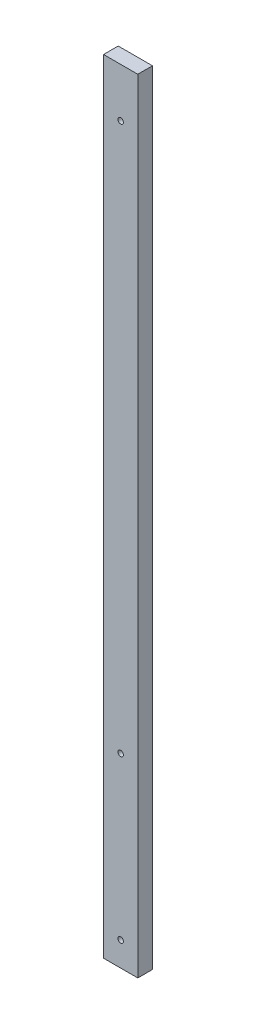
SolidWorks part; units mm, degrees
material "Oak"
ref_plane "Front Plane" through (0, 0, 0) normal (0, 0, 1) x (1, 0, 0)
ref_plane "Top Plane" through (0, 0, 0) normal (0, 1, 0) x (1, 0, 0)
ref_plane "Right Plane" through (0, 0, 0) normal (1, 0, 0) x (0, 0, -1)
sketch "Sketch1" plane through (0, 0, 0) normal (0, 1, 0) x (1, 0, 0)
  line L1 (-44.45, -19.05) -> (44.45, -19.05)
  line L2 (-44.45, -19.05) -> (-44.45, 19.05)
  line L3 (-44.45, 19.05) -> (44.45, 19.05)
  line L4 (44.45, -19.05) -> (44.45, 19.05)
  line L5 (-44.45, -19.05) -> (44.45, 19.05) construction
  line L6 (-44.45, 19.05) -> (44.45, -19.05) construction
  point P0 (0, 0)
  dimension "D1" = 38.1
  dimension "D2" = 88.9
extrude "Boss-Extrude1" add sketch "Sketch1" along normal blind 2032 contours L3 L4 L1 L2
sketch "Sketch2" plane through (0, 0, 19.05) normal (0, 0, 1) x (1, 0, 0)
  line L0 (0, 2032) -> (0, 0) construction
  line L1 (-44.45, 2032) -> (44.45, 2032) construction
  line L2 (-44.45, 0) -> (44.45, 0) construction
  circle A0 centre (0, 63.5) radius 7.1438
  circle A1 centre (0, 482.6) radius 7.1437
  circle A2 centre (0, 1905) radius 7.1438
  dimension "D1" = 14.2875
  dimension "D2" = 63.5
  dimension "D3" = 482.6
  dimension "D4" = 1905
extrude "Cut-Extrude1" cut sketch "Sketch2" against normal through all both and the other way through all
